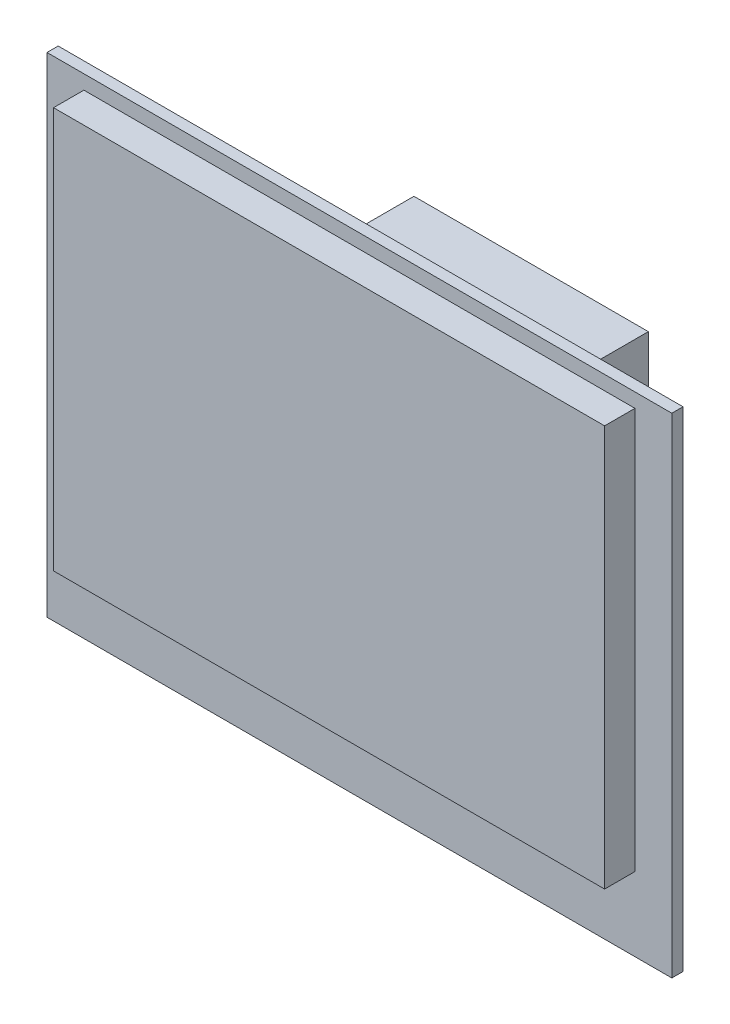
SolidWorks part; units mm, degrees
ref_plane "Front Plane" through (0, 0, 0) normal (0, 0, 1) x (1, 0, 0)
ref_plane "Top Plane" through (0, 0, 0) normal (0, 1, 0) x (1, 0, 0)
ref_plane "Right Plane" through (0, 0, 0) normal (1, 0, 0) x (0, 0, -1)
sketch "Sketch1" plane through (0, 0, 0) normal (0, 0, 1) x (1, 0, 0)
  line L1 (-43.9841, -34.43) -> (43.9841, -34.43)
  line L2 (-43.9841, -34.43) -> (-43.9841, 34.43)
  line L3 (-43.9841, 34.43) -> (43.9841, 34.43)
  line L4 (43.9841, -34.43) -> (43.9841, 34.43)
  line L5 (-43.9841, -34.43) -> (43.9841, 34.43) construction
  line L6 (-43.9841, 34.43) -> (43.9841, -34.43) construction
  point P0 (0, 0)
extrude "Boss-Extrude1" add sketch "Sketch1" along normal blind 1.5748
sketch "Sketch2" plane through (0, 0, 1.5748) normal (0, 0, 1) x (1, 0, 0)
  line L0 (43.9841, -34.43) -> (43.9841, 34.43) construction
  line L1 (-38.79, -24.05) -> (38.79, -24.05)
  line L2 (-38.79, -24.05) -> (-38.79, 32.43)
  line L3 (-38.79, 32.43) -> (38.79, 32.43)
  line L4 (38.79, -24.05) -> (38.79, 32.43)
  line L5 (38.79, 32.43) -> (43.9841, 32.43) construction
  line L6 (-38.79, 32.43) -> (-43.9841, 32.43) construction
  line L7 (-43.9841, 34.43) -> (-43.9841, -34.43) construction
  line L8 (43.9841, 34.43) -> (-43.9841, 34.43) construction
  point P0 (0, 0)
  dimension "D1" = 56.48
  dimension "D2" = 77.58
  dimension "D3" = 2
extrude "Boss-Extrude2" add sketch "Sketch2" along normal blind 4.27
sketch "Sketch3" plane through (0, 0, 0) normal (0, 0, -1) x (-1, 0, 0)
  line L0 (-43.9841, 34.43) -> (43.9841, 34.43) construction
  line L1 (2.7659, 32.28) -> (-30.2341, 32.28)
  line L2 (2.7659, 32.28) -> (2.7659, 23.32)
  line L3 (2.7659, 23.32) -> (-30.2341, 23.32)
  line L4 (-30.2341, 32.28) -> (-30.2341, 23.32)
  line L6 (-43.9841, -34.43) -> (-43.9841, 34.43) construction
  dimension "D1" = 8.96
  dimension "D2" = 33
  dimension "D3" = 2.15
  dimension "D4" = 13.75
extrude "Boss-Extrude3" add sketch "Sketch3" along normal blind 8.87
sketch "Sketch4" plane through (0, 0, 0) normal (0, 0, -1) x (-1, 0, 0)
  line L0 (-43.9841, 34.43) -> (43.9841, 34.43) construction
  line L1 (5.5459, 30.005) -> (14.0709, 30.005)
  line L2 (5.5459, 30.005) -> (5.5459, 24.78)
  line L3 (5.5459, 24.78) -> (14.0709, 24.78)
  line L4 (14.0709, 30.005) -> (14.0709, 24.78)
  line L6 (2.7659, 23.32) -> (2.7659, 32.28) construction
  dimension "D1" = 5.225
  dimension "D2" = 8.525
  dimension "D3" = 4.425
  dimension "D4" = 2.78
extrude "Boss-Extrude4" add sketch "Sketch4" along normal blind 4
